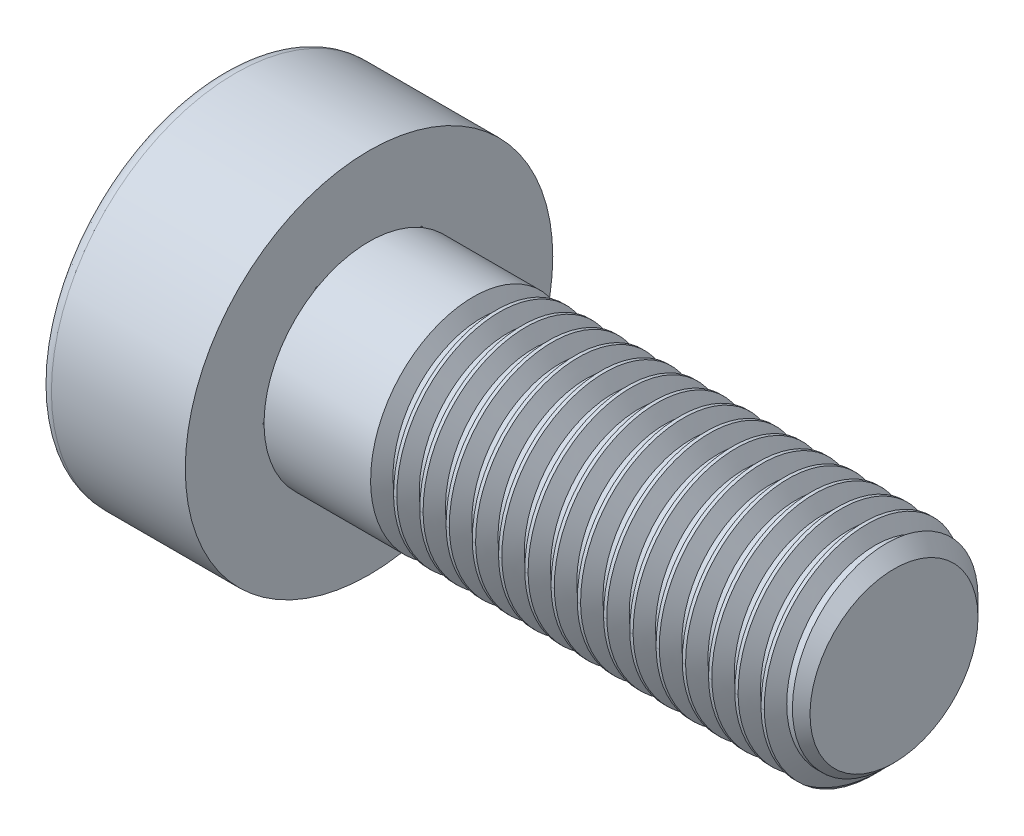
SolidWorks part; units mm, degrees
ref_plane "前视基准面" through (0, 0, 0) normal (0, 0, 1) x (1, 0, 0)
ref_plane "上视基准面" through (0, 0, 0) normal (0, 1, 0) x (1, 0, 0)
ref_plane "右视基准面" through (0, 0, 0) normal (1, 0, 0) x (0, 0, -1)
sketch "草图1" plane through (0, 0, 0) normal (1, 0, 0) x (0, 0, -1)
  line L1 (2.0207, 0) -> (1.0104, 1.75)
  line L2 (1.0104, 1.75) -> (-1.0104, 1.75)
  line L3 (-1.0104, 1.75) -> (-2.0207, 0)
  line L4 (-2.0207, 0) -> (-1.0104, -1.75)
  line L5 (-1.0104, -1.75) -> (1.0104, -1.75)
  line L6 (1.0104, -1.75) -> (2.0207, 0)
  circle A0 centre (0, 0) radius 3.5
  dimension "D1" = 3.5
extrude "拉伸1" add sketch "草图1" along normal blind 2.8
sketch "草图2" plane through (0, 0, 0) normal (-1, 0, 0) x (0, 0, 1)
  circle A0 centre (0, 0) radius 3.5
  dimension "D1" = 7
sketch "草图4" plane through (2.8, 0, 0) normal (1, 0, 0) x (0, 0, -1)
  circle A0 centre (0, 0) radius 2
  dimension "D1" = 4
extrude "拉伸2" add sketch "草图4" along normal blind 10
chamfer "倒角1" distance 0.4 angle 45 1 edges at (12.8, 0, -2)
sketch "草图5" plane through (0, 0, 0) normal (0, 1, 0) x (1, 0, 0)
  line L0 (217.2267, 2) -> (226.9644, 2) construction
  line L1 (12.4, 2) -> (2.8, 2) construction
  line L2 (12.8, 12.6777) -> (12.8, 22.4507) construction
  line L3 (12.8, -1.6) -> (12.8, 1.6) construction
  line L4 (12.7375, 1.7294) -> (12.5812, 2)
  line L5 (12.8625, 1.7294) -> (13.0187, 2)
  line L6 (12.5812, 2) -> (13.0187, 2)
  line L7 (12.7375, 1.7294) -> (12.8625, 1.7294)
  dimension "D1" = 30
  dimension "D2" = 30
  dimension "D3" = 0.4375
  dimension "D4" = 0.125
sketch "草图6" plane through (12.8, 0, 0) normal (1, 0, 0) x (0, 0, -1)
  circle A0 centre (0, 0) radius 2
  dimension "D1" = 4
curve "螺旋线1" pitch 0.5 height 8 radius 2 centre (12.8, 0, 0) axis (-1, 0, 0) start towards (0, 0, -1)
sweep "切除-扫描1" cut profiles "草图5" path "螺旋线1"
fillet "圆角1" radius 0.2 rebuild error yes type face fillet
fillet "圆角2" radius 0.25 1 edges at (0, 0, -3.5)
fillet "圆角3" radius 0.125 6 edges at (0, -0.875, -1.5155) (0, 0.875, -1.5155) (0, 1.75, 0) (0, 0.875, 1.5155) (0, -0.875, 1.5155) (0, -1.75, 0)
